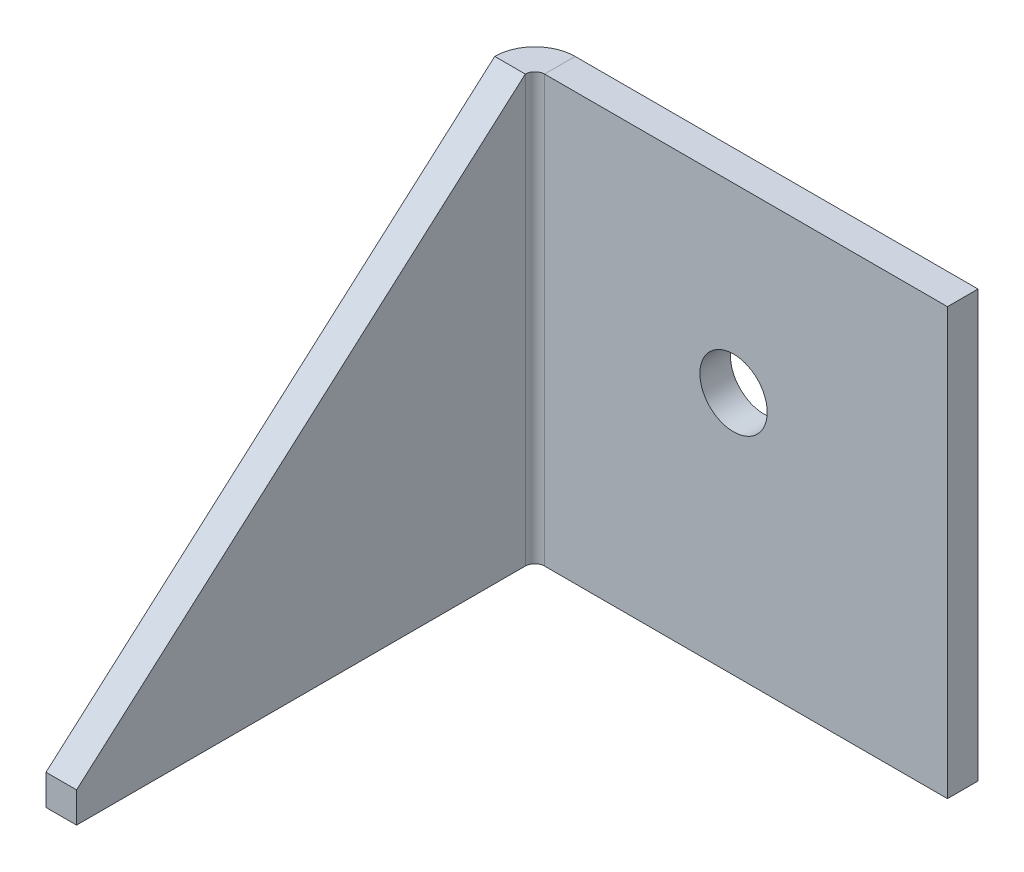
SolidWorks part; units mm, degrees
note: The reader was unsure of these and kept them because the rebuilt part matched: flange length of "Edge-Flange1".
material "6061-T6 (SS)"
ref_plane "X-Y Datum" through (0, 0, 0) normal (0, 0, 1) x (1, 0, 0)
ref_plane "X-Z Datum" through (0, 0, 0) normal (0, 1, 0) x (1, 0, 0)
ref_plane "Y-Z Datum" through (0, 0, 0) normal (1, 0, 0) x (0, 0, -1)
sketch "Sketch1" plane through (0, 0, 0) normal (0, 0, 1) x (1, 0, 0)
  line L1 (-21.4312, -22.1374) -> (21.4312, -22.1374)
  line L2 (-21.4312, -22.1374) -> (-21.4312, 22.1374)
  line L3 (-21.4312, 22.1374) -> (21.4312, 22.1374)
  line L4 (21.4312, -22.1374) -> (21.4312, 22.1374)
  line L5 (-21.4312, -22.1374) -> (21.4312, 22.1374) construction
  line L6 (-21.4312, 22.1374) -> (21.4312, -22.1374) construction
  circle A1 centre (-0.7937, 3.2626) radius 3
  point P0 (0, 0)
  dimension "D3" = 6
  dimension "D1" = 20.6375
  dimension "D2" = 42.8625
  dimension "D4" = 25.4
  dimension "D5" = 44.2747
base flange "Base-Flange1" sketch "Sketch1" thickness 3.175 reverse thickness direction yes parameters "D1"=10
edge flange "Edge-Flange1" sketch "Sketch8" flange angle 90 flange length 50.8 flange position material outside bend radius 1 thickness 3.175 parameters "D6"=10
sketch "Sketch8" plane through (-21.4312, 0, 3.175) normal (1, 0, 0) x (0, 1, 0)
  line L2 (-22.1374, 0) -> (-22.1374, 47.625)
  line L3 (-22.1374, 47.625) -> (22.1374, 47.625)
  line L4 (22.1374, 47.625) -> (22.1374, 0)
  line L5 (22.1374, 0) -> (-22.1374, 0) construction
  line L6 (22.1374, 0) -> (-22.1374, 0)
bend "EdgeBend1" bend radius 1 bend angle 90 parameters "D5"=1
sketch "Sketch10" plane through (-24.6062, 0, 0) normal (-1, 0, 0) x (0, 0, 1)
  line L0 (50.8, -18.9624) -> (4.175, 22.1374)
  line L1 (50.8, -22.1374) -> (50.8, -18.9624)
  line L2 (50.8, 22.1374) -> (50.8, -22.1374) construction
  dimension "D1" = 3.175
extrude "Cut-Extrude1" cut sketch "Sketch10" against normal blind 3.175 and the other way through all
edge flange "Edge-Flange2" [suppressed] sketch "Sketch13" flange angle 90 flange position material outside bend radius 1 thickness 3.175
sketch "Sketch13" [suppressed] plane through (21.4312, 0, 3.175) normal (-1, 0, 0) x (0, -1, 0)
  line L2 (-22.1374, 0) -> (-22.1374, 47.625)
  line L3 (-22.1374, 47.625) -> (22.1374, 47.625)
  line L4 (22.1374, 47.625) -> (22.1374, 0)
  line L5 (22.1374, 0) -> (-22.1374, 0) construction
  line L6 (22.1374, 0) -> (-22.1374, 0)
bend "EdgeBend2" [suppressed] bend radius 1 bend angle 90 parameters "D5"=1, "D6"=10, "D7"=50.8
sketch "Sketch14" [suppressed] plane through (24.6062, 0, 0) normal (1, 0, 0) x (0, 0, -1)
  line L1 (-50.8, -22.1374) -> (-50.8, -18.9624)
  line L2 (-50.8, -22.1374) -> (-50.8, 22.1374) construction
  line L3 (-50.8, -18.9624) -> (-4.175, 22.1374)
  dimension "D1" = 3.175
extrude "Cut-Extrude3" [suppressed] cut sketch "Sketch14" against normal blind 3.175 and the other way through all
edge flange "Edge-Flange3" [suppressed] sketch "Sketch17" flange angle 90 flange position material outside bend radius 1 thickness 3.175
sketch "Sketch17" [suppressed] plane through (21.4312, 0, 3.175) normal (-1, 0, 0) x (0, -1, 0)
  line L2 (-22.1374, 0) -> (-22.1374, 47.625)
  line L3 (-22.1374, 47.625) -> (22.1374, 47.625)
  line L4 (22.1374, 47.625) -> (22.1374, 0)
  line L5 (22.1374, 0) -> (-22.1374, 0) construction
  line L6 (22.1374, 0) -> (-22.1374, 0)
bend "EdgeBend3" [suppressed] bend radius 1 bend angle 90 parameters "D5"=1, "D6"=10, "D7"=50.8
sketch "Sketch18" [suppressed] plane through (24.6062, 0, 0) normal (1, 0, 0) x (0, 0, -1)
  line L0 (-50.8, -18.9624) -> (-4.175, 22.1374)
  line L1 (-50.8, -22.1374) -> (-50.8, -18.9624)
  line L2 (-50.8, -22.1374) -> (-50.8, 22.1374) construction
  dimension "D1" = 3.175
extrude "Cut-Extrude4" [suppressed] cut sketch "Sketch18" against normal blind 3.175 and the other way through all
edge flange "Edge-Flange5" [suppressed] sketch "Sketch25" flange angle 90 flange position material outside bend radius 1 thickness 3.175
sketch "Sketch25" [suppressed] plane through (-21.4312, 0, 3.175) normal (1, 0, 0) x (0, 1, 0)
  line L2 (-22.1374, 0) -> (-22.1374, 47.625)
  line L3 (-22.1374, 47.625) -> (22.1374, 47.625)
  line L4 (22.1374, 47.625) -> (22.1374, 0)
  line L5 (22.1374, 0) -> (-22.1374, 0) construction
  line L6 (22.1374, 0) -> (-22.1374, 0)
bend "EdgeBend5" [suppressed] bend radius 1 bend angle 90 parameters "D5"=1, "D6"=10, "D7"=50.8
sketch "Sketch26" [suppressed] plane through (-24.6062, 0, 0) normal (-1, 0, 0) x (0, 0, 1)
  line L0 (4.175, 22.1374) -> (50.8, -18.9624)
  line L1 (50.8, -22.1374) -> (50.8, -18.9624)
  line L2 (50.8, 22.1374) -> (50.8, -22.1374) construction
  dimension "D1" = 3.175
extrude "Cut-Extrude6" [suppressed] cut sketch "Sketch26" against normal blind 3.175 and the other way through all
hole_wizard "M6 Clearance Hole6" positions "Sketch57" profile "Sketch52" hole size "M6" standard "ANSI Metric" end condition through all
sketch "Sketch57" plane through (0, 0, 3.175) normal (0, 0, 1) x (1, 0, 0)
  point P0 (-0.7937, 3.2626)
sketch "Sketch52" plane through (-0.7937, 3.2626, 3.175) normal (1, 0, 0) x (0, -1, 0)
  line L0 (0, 0) -> (0, 3.175)
  line L1 (0, 3.175) -> (3.5, 3.175)
  line L2 (3.5, 3.175) -> (3.5, 0)
  line L5 (3.5, 0) -> (0, 0)
  line L11 (0, -6.35) -> (0, 107.95) construction
  dimension "Thru Hole Dia." = 7
  dimension "Thru Hole Depth" = 3.175
sketch "Bend-Lines1" [suppressed] plane through (0, 0, 0) normal (0, 1, 0) x (1, 0, 0)
sketch "Bounding-Box1" [suppressed] plane through (0, 0, 0) normal (0, 1, 0) x (1, 0, 0)
sheet metal parameters "Sheet-Metal1" thickness 3.175 parameters "D1"=10
flat pattern "Flat-Pattern1" [suppressed]
sketch "Bend-Lines2" plane through (0, 0, 0) normal (0, 1, 0) x (1, 0, 0)
sketch3d "Bounding-Box2" [suppressed]
  line L0 (-21.4312, 22.1374, 0) -> (-21.4312, -22.1374, 0) construction
  line L1 (21.4312, 22.1374, 0) -> (21.4312, -22.1374, 0) construction
  line L2 (-21.4312, 22.1374, 0) -> (21.4312, 22.1374, 0) construction
  line L3 (-21.4312, -22.1374, 0) -> (21.4312, -22.1374, 0) construction
sheet metal parameters "Sheet-Metal2" thickness 3.175 parameters "D1"=10
flat pattern "Flat-Pattern1"
sketch "Bend-Lines2" plane through (0, 0, 0) normal (0, 0, -1) x (-1, 0, 0)
  line L0 (23.8922, -22.1374) -> (23.8922, 22.1374) construction
  line L1 (23.8922, -22.1374) -> (23.8922, 22.1374) construction
sketch3d "Bounding-Box2" [suppressed]
  line L0 (72.5494, -22.1374, 0) -> (-22.86, -22.1374, 0) construction
  line L1 (72.5494, 22.1374, 0) -> (-22.86, 22.1374, 0) construction
  line L2 (72.5494, -22.1374, 0) -> (72.5494, 22.1374, 0) construction
  line L3 (-22.86, -22.1374, 0) -> (-22.86, 22.1374, 0) construction
bend of the flat pattern "Flatten-<EdgeBend1>1"
sheet metal parameters "Sheet-Metal3" thickness 3.175 parameters "D1"=10
flat pattern "Flat-Pattern1" [suppressed]
sketch "Bend-Lines2" plane through (-21.4312, 0, 0) normal (1, 0, 0) x (0, 0, -1)
  point P2 (-2.1428, 22.1374)
  point P3 (-2.1428, -22.1374)
sketch3d "Bounding-Box2" [suppressed]
  line L0 (-50.8, -18.9624, 0) -> (-4.175, -18.9624, 0) construction
  line L1 (-50.8, 22.1374, 0) -> (-4.175, 22.1374, 0) construction
  line L2 (-50.8, -18.9624, 0) -> (-50.8, 22.1374, 0) construction
  line L3 (-4.175, -18.9624, 0) -> (-4.175, 22.1374, 0) construction
bend of the flat pattern "Flatten-<EdgeBend1>1"
sheet metal parameters "Sheet-Metal4" thickness 3.175 parameters "D1"=10
flat pattern "Flat-Pattern1" [suppressed]
sketch "Bend-Lines2" plane through (0, 0, 0) normal (0, 0, -1) x (-1, 0, 0)
  line L0 (-22.4635, 22.1374) -> (-22.4635, -22.1374) construction
  line L1 (-22.4635, 22.1374) -> (-22.4635, -22.1374) construction
sketch3d "Bounding-Box2" [suppressed]
  line L0 (21.4312, -22.1374, 0) -> (-71.1207, -22.1374, 0) construction
  line L1 (21.4312, 22.1374, 0) -> (-71.1207, 22.1374, 0) construction
  line L2 (21.4312, -22.1374, 0) -> (21.4312, 22.1374, 0) construction
  line L3 (-71.1207, -22.1374, 0) -> (-71.1207, 22.1374, 0) construction
bend of the flat pattern "Flatten-<EdgeBend2>1"
sketch "Sketch14-1" [suppressed] plane through (20.3207, 0, 0) normal (0, 0, -1) x (-1, 0, 0)
  line L0 (-50.8, 22.1374) -> (-4.175, -22.1374)
sheet metal parameters "Sheet-Metal6" thickness 3.175 parameters "D1"=10
flat pattern "Flat-Pattern1" [suppressed]
sketch "Bend-Lines2" plane through (0, 0, 0) normal (0, 0, -1) x (-1, 0, 0)
  line L0 (-22.4635, 22.1374) -> (-22.4635, -22.1374) construction
  line L1 (-22.4635, 22.1374) -> (-22.4635, -22.1374) construction
sketch3d "Bounding-Box2" [suppressed]
  line L0 (21.4312, -22.1374, 0) -> (-71.1207, -22.1374, 0) construction
  line L1 (21.4312, 22.1374, 0) -> (-71.1207, 22.1374, 0) construction
  line L2 (21.4312, -22.1374, 0) -> (21.4312, 22.1374, 0) construction
  line L3 (-71.1207, -22.1374, 0) -> (-71.1207, 22.1374, 0) construction
bend of the flat pattern "Flatten-<EdgeBend2>1"
sketch "Sketch14-1" plane through (20.3207, 0, 0) normal (0, 0, -1) x (-1, 0, 0)
  line L1 (-50.8, -22.1374) -> (-50.8, -18.9624)
  line L3 (-50.8, -18.9624) -> (-4.175, 22.1374)
  dimension "D1" = 3.175
sheet metal parameters "Sheet-Metal7" thickness 3.175 parameters "D1"=10
flat pattern "Flat-Pattern1"
sketch "Bend-Lines2" plane through (0, 0, 0) normal (0, 0, -1) x (-1, 0, 0)
  line L0 (-22.4635, 22.1374) -> (-22.4635, -22.1374) construction
  line L1 (-22.4635, 22.1374) -> (-22.4635, -22.1374) construction
sketch3d "Bounding-Box2" [suppressed]
  line L0 (21.4312, -22.1374, 0) -> (-71.1207, -22.1374, 0) construction
  line L1 (21.4312, 22.1374, 0) -> (-71.1207, 22.1374, 0) construction
  line L2 (21.4312, -22.1374, 0) -> (21.4312, 22.1374, 0) construction
  line L3 (-71.1207, -22.1374, 0) -> (-71.1207, 22.1374, 0) construction
bend of the flat pattern "Flatten-<EdgeBend3>1"
sheet metal parameters "Sheet-Metal8" thickness 3.175 parameters "D1"=10
flat pattern "Flat-Pattern1"
sketch "Bend-Lines2" plane through (0, 0, 0) normal (0, 0, -1) x (-1, 0, 0)
  line L0 (-22.4635, 22.1374) -> (-22.4635, -22.1374) construction
  line L1 (-22.4635, 22.1374) -> (-22.4635, -22.1374) construction
sketch3d "Bounding-Box2" [suppressed]
  line L0 (21.4312, -22.1374, 0) -> (-71.1207, -22.1374, 0) construction
  line L1 (21.4312, 22.1374, 0) -> (-71.1207, 22.1374, 0) construction
  line L2 (21.4312, -22.1374, 0) -> (21.4312, 22.1374, 0) construction
  line L3 (-71.1207, -22.1374, 0) -> (-71.1207, 22.1374, 0) construction
bend of the flat pattern "Flatten-<EdgeBend3>1"
sheet metal parameters "Sheet-Metal13" thickness 3.175 parameters "D1"=10
flat pattern "Flat-Pattern1"
sketch "Bend-Lines2" plane through (0, 0, 0) normal (0, 0, -1) x (-1, 0, 0)
  line L0 (22.4635, -22.1374) -> (22.4635, 22.1374) construction
  line L1 (22.4635, -22.1374) -> (22.4635, 22.1374) construction
sketch3d "Bounding-Box2" [suppressed]
  line L0 (71.1207, -22.1374, 0) -> (-21.4312, -22.1374, 0) construction
  line L1 (71.1207, 22.1374, 0) -> (-21.4312, 22.1374, 0) construction
  line L2 (71.1207, -22.1374, 0) -> (71.1207, 22.1374, 0) construction
  line L3 (-21.4312, -22.1374, 0) -> (-21.4312, 22.1374, 0) construction
bend of the flat pattern "Flatten-<EdgeBend5>1"
sheet metal parameters "Sheet-Metal14" thickness 3.175 parameters "D1"=10
flat pattern "Flat-Pattern1"
sketch "Bend-Lines2" plane through (0, 0, 0) normal (0, 0, -1) x (-1, 0, 0)
  line L0 (22.4635, -22.1374) -> (22.4635, 22.1374) construction
  line L1 (22.4635, -22.1374) -> (22.4635, 22.1374) construction
sketch3d "Bounding-Box2" [suppressed]
  line L0 (71.1207, -22.1374, 0) -> (-21.4312, -22.1374, 0) construction
  line L1 (71.1207, 22.1374, 0) -> (-21.4312, 22.1374, 0) construction
  line L2 (71.1207, -22.1374, 0) -> (71.1207, 22.1374, 0) construction
  line L3 (-21.4312, -22.1374, 0) -> (-21.4312, 22.1374, 0) construction
bend of the flat pattern "Flatten-<EdgeBend5>1"
sheet metal parameters "Sheet-Metal20" thickness 3.175 parameters "D1"=10
flat pattern "Flat-Pattern1" [suppressed]
sketch "Bend-Lines2" plane through (-21.4312, 0, 0) normal (1, 0, 0) x (0, 0, -1)
  line L0 (-2.1428, 22.1374) -> (-2.1428, -22.1374) construction
  line L1 (-2.1428, 22.1374) -> (-2.1428, -22.1374) construction
sketch3d "Bounding-Box2" [suppressed]
  line L0 (-50.8, -22.1374, 0) -> (41.7519, -22.1374, 0) construction
  line L1 (-50.8, 22.1374, 0) -> (41.7519, 22.1374, 0) construction
  line L2 (-50.8, -22.1374, 0) -> (-50.8, 22.1374, 0) construction
  line L3 (41.7519, -22.1374, 0) -> (41.7519, 22.1374, 0) construction
bend of the flat pattern "Flatten-<EdgeBend1>1"
sketch "Sketch55-1" plane through (-21.4313, 0, -20.3207) normal (1, 0, 0) x (0, 0, -1)
  point P0 (-0.7937, 3.2626)
